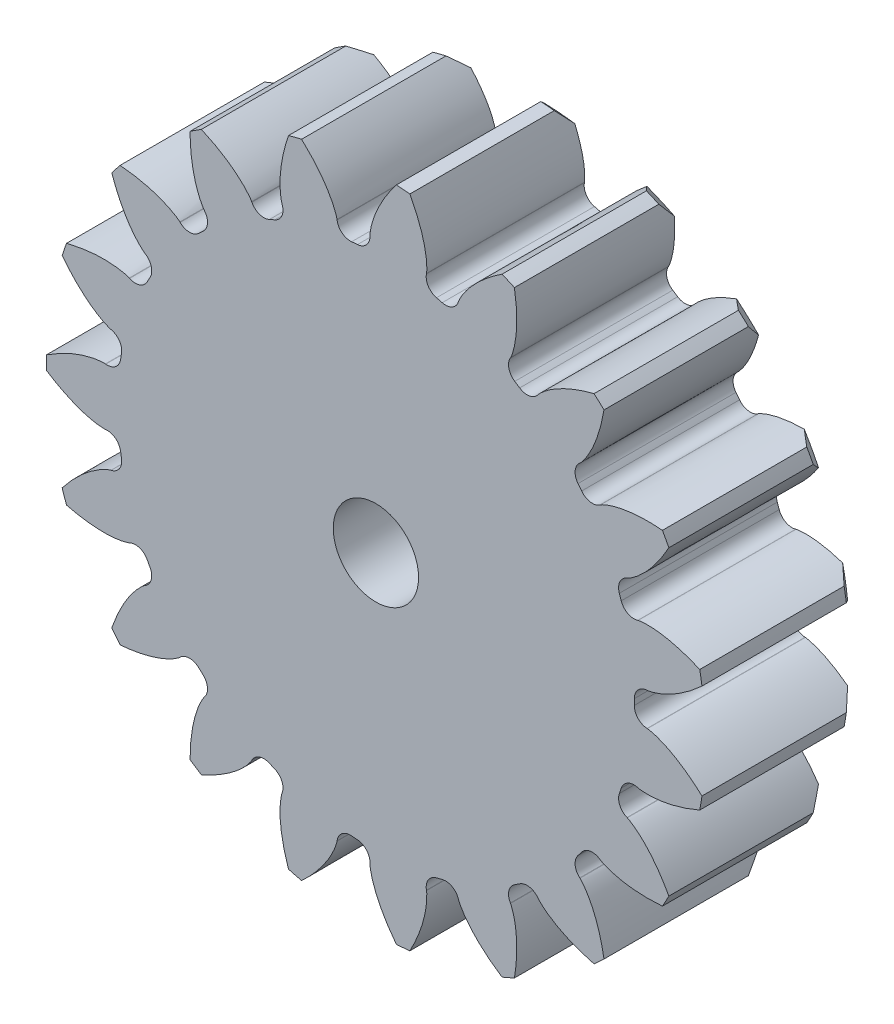
SolidWorks part; units mm, degrees
ref_plane "Front Plane" through (0, 0, 0) normal (0, 0, 1) x (1, 0, 0)
ref_plane "Top Plane" through (0, 0, 0) normal (0, 1, 0) x (1, 0, 0)
ref_plane "Right Plane" through (0, 0, 0) normal (1, 0, 0) x (0, 0, -1)
ref_axis "Axis1" through (0, 0, -0.2618) along (0, 0, 1)
sketch "Sketch1" plane through (0, 0, 0) normal (0, 0, 1) x (1, 0, 0)
  circle A0 centre (0, 0) radius 10.5
  dimension "D1" = 21
extrude "Boss-Extrude1" add sketch "Sketch1" along normal blind 5
sketch "Sketch2" plane through (0, 0, 5) normal (0, 0, 1) x (1, 0, 0)
  line L0 (0, 0) -> (8.2385, 0.4346) construction
  line L1 (8.2385, 0.4346) -> (8.598, 0.4535)
  line L2 (0, 0) -> (8.2385, -0.4346) construction
  line L3 (8.2385, -0.4346) -> (8.598, -0.4535)
  circle A0 centre (0, 0) radius 9.5 construction
  circle A1 centre (0, 0) radius 10.5 construction
  circle A2 centre (0, 0) radius 8.6099 construction
  circle A3 centre (0, 0) radius 8.25 construction
  arc A4 (8.2385, 0.4346) -> (8.2385, -0.4346) centre (0, 0) cw
  arc A5 (10.3953, 1.479) -> (10.3953, -1.479) centre (0, 0) cw
  spline S0 degree 4 poles (8.598, 0.4535) (8.6011, 0.4537) (8.6097, 0.4545) (8.6261, 0.4564) (8.6527, 0.4603) (8.7019, 0.4694) (8.7606, 0.483) (8.8264, 0.5011) (8.8966, 0.5233) (8.9562, 0.544) (9.0154, 0.5662) (9.074, 0.5897) (9.1445, 0.6198) (9.2284, 0.6582) (9.3256, 0.7063) (9.4345, 0.7648) (9.5442, 0.8285) (9.6509, 0.8946) (9.7572, 0.9651) (9.8591, 1.0361) (9.9633, 1.1136) (10.0586, 1.1871) (10.1636, 1.2736) (10.2478, 1.3447) (10.3567, 1.4428) (10.4204, 1.502) (10.4941, 1.5728) (10.5265, 1.605) (10.5464, 1.6249) knots 0 0 0 0 0 0.005377 0.015084 0.028532 0.04661 0.092111 0.119476 0.146842 0.174209 0.201575 0.228941 0.256307 0.307035 0.361767 0.4165 0.471232 0.525964 0.580697 0.635429 0.690161 0.744894 0.799626 0.854358 0.909091 0.954545 1 1 1 1 1 construction
  spline S1 degree 4 poles (8.598, 0.4535) (8.6011, 0.4537) (8.6097, 0.4545) (8.6261, 0.4564) (8.6527, 0.4603) (8.7019, 0.4694) (8.7606, 0.483) (8.8264, 0.5011) (8.8966, 0.5233) (8.9562, 0.544) (9.0154, 0.5662) (9.074, 0.5897) (9.1445, 0.6198) (9.2284, 0.6582) (9.3256, 0.7063) (9.4345, 0.7648) (9.5442, 0.8285) (9.6509, 0.8946) (9.7572, 0.9651) (9.8591, 1.0361) (9.9633, 1.1136) (10.0586, 1.1871) (10.1636, 1.2736) (10.2478, 1.3447) (10.3331, 1.4215) (10.3743, 1.4594) (10.3953, 1.479) knots 0 0 0 0 0 0.005377 0.015084 0.028532 0.04661 0.092111 0.119476 0.146842 0.174209 0.201575 0.228941 0.256307 0.307035 0.361767 0.4165 0.471232 0.525964 0.580697 0.635429 0.690161 0.744894 0.799626 0.854358 0.909091 0.909091 0.909091 0.909091 0.909091
  spline S2 degree 4 poles (8.598, -0.4535) (8.6011, -0.4537) (8.6097, -0.4545) (8.6261, -0.4564) (8.6527, -0.4603) (8.7019, -0.4694) (8.7606, -0.483) (8.8264, -0.5011) (8.8966, -0.5233) (8.9562, -0.544) (9.0154, -0.5662) (9.074, -0.5897) (9.1445, -0.6198) (9.2284, -0.6582) (9.3256, -0.7063) (9.4345, -0.7648) (9.5442, -0.8285) (9.6509, -0.8946) (9.7572, -0.9651) (9.8591, -1.0361) (9.9633, -1.1136) (10.0586, -1.1871) (10.1636, -1.2736) (10.2478, -1.3447) (10.3567, -1.4428) (10.4204, -1.502) (10.4941, -1.5728) (10.5265, -1.605) (10.5464, -1.6249) knots 0 0 0 0 0 0.005377 0.015084 0.028532 0.04661 0.092111 0.119476 0.146842 0.174209 0.201575 0.228941 0.256307 0.307035 0.361767 0.4165 0.471232 0.525964 0.580697 0.635429 0.690161 0.744894 0.799626 0.854358 0.909091 0.954545 1 1 1 1 1 construction
  spline S3 degree 4 poles (8.598, -0.4535) (8.6011, -0.4537) (8.6097, -0.4545) (8.6261, -0.4564) (8.6527, -0.4603) (8.7019, -0.4694) (8.7606, -0.483) (8.8264, -0.5011) (8.8966, -0.5233) (8.9562, -0.544) (9.0154, -0.5662) (9.074, -0.5897) (9.1445, -0.6198) (9.2284, -0.6582) (9.3256, -0.7063) (9.4345, -0.7648) (9.5442, -0.8285) (9.6509, -0.8946) (9.7572, -0.9651) (9.8591, -1.0361) (9.9633, -1.1136) (10.0586, -1.1871) (10.1636, -1.2736) (10.2478, -1.3447) (10.3331, -1.4215) (10.3743, -1.4594) (10.3953, -1.479) knots 0 0 0 0 0 0.005377 0.015084 0.028532 0.04661 0.092111 0.119476 0.146842 0.174209 0.201575 0.228941 0.256307 0.307035 0.361767 0.4165 0.471232 0.525964 0.580697 0.635429 0.690161 0.744894 0.799626 0.854358 0.909091 0.909091 0.909091 0.909091 0.909091
  dimension "D1" = 21
  dimension "D2" = 19
  dimension "D3" = 17.2198
  dimension "D4" = 16.5
extrude "Cut-Extrude1" cut sketch "Sketch2" against normal through all
fillet "Fillet1" radius 0.3557 1 edges at (8.2385, 0.4346, 2.5)
fillet "Fillet2" radius 0.3557 1 edges at (8.2385, -0.4346, 2.5)
pattern_circular "CirPattern1" count 19 over 360 about axis through (0, 0, 5) along (0, 0, -1) of "Cut-Extrude1", "Fillet1", "Fillet2"
sketch "Sketch4" plane through (0, 0, 5) normal (0, 0, 1) x (1, 0, 0)
  circle A0 centre (0, 0) radius 1.35
  dimension "D1" = 2.7
extrude "Bore" cut sketch "Sketch4" against normal through all
sketch "Sketch5" plane through (0, 0, 5) normal (0, 0, 1) x (1, 0, 0)
  line L44 (8.298, 2.2953) -> (8.2874, 2.2923)
  line L45 (8.298, 2.2953) -> (8.2874, 2.2923)
  line L46 (7.9479, 3.2813) -> (7.9582, 3.2854)
  line L47 (7.9479, 3.2813) -> (7.9582, 3.2854)
  line L108 (-2.9728, 8.0801) -> (-2.9688, 8.0698)
  line L109 (-3.9264, 7.6498) -> (-3.9314, 7.6597)
  line L110 (-5.4353, 6.6771) -> (-5.4282, 6.6686)
  line L111 (-6.1975, 5.9604) -> (-6.2054, 5.9681)
  line L112 (-7.3089, 4.5505) -> (-7.2994, 4.5447)
  line L113 (-7.7971, 3.6251) -> (-7.8071, 3.6299)
  line L114 (-8.3904, 1.9307) -> (-8.3796, 1.9283)
  line L115 (-8.5517, 0.897) -> (-8.5627, 0.8982)
  line L116 (-8.5627, -0.8982) -> (-8.5517, -0.897)
  line L117 (-8.3796, -1.9283) -> (-8.3904, -1.9307)
  line L118 (-7.8071, -3.6299) -> (-7.7971, -3.6251)
  line L119 (-7.2994, -4.5447) -> (-7.3089, -4.5505)
  line L120 (-6.2054, -5.9681) -> (-6.1975, -5.9604)
  line L121 (-5.4282, -6.6686) -> (-5.4353, -6.6771)
  line L122 (-3.9314, -7.6597) -> (-3.9264, -7.6498)
  line L123 (-2.9688, -8.0698) -> (-2.9728, -8.0801)
  line L124 (-1.2313, -8.5212) -> (-1.2298, -8.5102)
  line L125 (-0.1877, -8.5965) -> (-0.1881, -8.6076)
  line L126 (1.6023, -8.4592) -> (1.6001, -8.4484)
  line L127 (2.6137, -8.1917) -> (2.617, -8.2023)
  line L128 (4.2622, -7.4806) -> (4.2566, -7.4711)
  line L129 (5.132, -6.8992) -> (5.1385, -6.9081)
  line L130 (6.4602, -5.6914) -> (6.4518, -5.6842)
  line L131 (7.0941, -4.859) -> (7.1031, -4.8653)
  line L132 (7.9582, -3.2854) -> (7.9479, -3.2813)
  line L133 (8.2874, -2.2923) -> (8.298, -2.2953)
  line L134 (8.5937, -0.5234) -> (8.5827, -0.5228)
  line L135 (8.5827, 0.5228) -> (8.5937, 0.5234)
  line L136 (7.1031, 4.8653) -> (7.0941, 4.859)
  line L137 (6.4518, 5.6842) -> (6.4602, 5.6914)
  line L138 (5.1385, 6.9081) -> (5.132, 6.8992)
  line L139 (4.2566, 7.4711) -> (4.2622, 7.4806)
  line L140 (2.617, 8.2023) -> (2.6137, 8.1917)
  line L141 (1.6001, 8.4484) -> (1.6023, 8.4592)
  line L142 (-0.1881, 8.6076) -> (-0.1877, 8.5965)
  line L143 (-1.2298, 8.5102) -> (-1.2313, 8.5212)
  line L144 (-2.9728, 8.0801) -> (-2.9688, 8.0698)
  line L145 (-3.9264, 7.6498) -> (-3.9314, 7.6597)
  line L146 (-5.4353, 6.6771) -> (-5.4282, 6.6686)
  line L147 (-6.1975, 5.9604) -> (-6.2054, 5.9681)
  line L148 (-7.3089, 4.5505) -> (-7.2994, 4.5447)
  line L149 (-7.7971, 3.6251) -> (-7.8071, 3.6299)
  line L150 (-8.3904, 1.9307) -> (-8.3796, 1.9283)
  line L151 (-8.5517, 0.897) -> (-8.5627, 0.8982)
  line L152 (-8.5627, -0.8982) -> (-8.5517, -0.897)
  line L153 (-8.3796, -1.9283) -> (-8.3904, -1.9307)
  line L154 (-7.8071, -3.6299) -> (-7.7971, -3.6251)
  line L155 (-7.2994, -4.5447) -> (-7.3089, -4.5505)
  line L156 (-6.2054, -5.9681) -> (-6.1975, -5.9604)
  line L157 (-5.4282, -6.6686) -> (-5.4353, -6.6771)
  line L158 (-3.9314, -7.6597) -> (-3.9264, -7.6498)
  line L159 (-2.9688, -8.0698) -> (-2.9728, -8.0801)
  line L160 (-1.2313, -8.5212) -> (-1.2298, -8.5102)
  line L161 (-0.1877, -8.5965) -> (-0.1881, -8.6076)
  line L162 (1.6023, -8.4592) -> (1.6001, -8.4484)
  line L163 (2.6137, -8.1917) -> (2.617, -8.2023)
  line L164 (4.2622, -7.4806) -> (4.2566, -7.4711)
  line L165 (5.132, -6.8992) -> (5.1385, -6.9081)
  line L166 (6.4602, -5.6914) -> (6.4518, -5.6842)
  line L167 (7.0941, -4.859) -> (7.1031, -4.8653)
  line L168 (7.9582, -3.2854) -> (7.9479, -3.2813)
  line L169 (8.2874, -2.2923) -> (8.298, -2.2953)
  line L170 (8.5937, -0.5234) -> (8.5827, -0.5228)
  line L171 (8.5827, 0.5228) -> (8.5937, 0.5234)
  line L172 (7.1031, 4.8653) -> (7.0941, 4.859)
  line L173 (6.4518, 5.6842) -> (6.4602, 5.6914)
  line L174 (5.1385, 6.9081) -> (5.132, 6.8992)
  line L175 (4.2566, 7.4711) -> (4.2622, 7.4806)
  line L176 (2.617, 8.2023) -> (2.6137, 8.1917)
  line L177 (1.6001, 8.4484) -> (1.6023, 8.4592)
  line L178 (-0.1881, 8.6076) -> (-0.1877, 8.5965)
  line L179 (-1.2298, 8.5102) -> (-1.2313, 8.5212)
  arc A88 (7.7665, 2.568) -> (8.2874, 2.2923) centre (8.1706, 2.7016) ccw
  arc A89 (7.7665, 2.568) -> (8.2874, 2.2923) centre (8.1706, 2.7016) ccw
  arc A90 (7.7665, 2.568) -> (7.7061, 2.7437) centre (0, 0) ccw
  arc A91 (7.7665, 2.568) -> (7.7061, 2.7437) centre (0, 0) ccw
  arc A92 (7.9479, 3.2813) -> (7.7061, 2.7437) centre (8.1071, 2.8865) ccw
  arc A93 (7.9479, 3.2813) -> (7.7061, 2.7437) centre (8.1071, 2.8865) ccw
  arc A94 (9.2728, 4.7749) -> (9.0692, 5.1512) centre (0, 0) ccw
  arc A95 (9.2728, 4.7749) -> (9.0692, 5.1512) centre (0, 0) ccw
  circle A144 centre (0, 0) radius 21
  arc A216 (-2.3525, 10.1612) -> (-2.7673, 10.0562) centre (0, 0) ccw
  arc A217 (-3.2006, 7.5279) -> (-2.9688, 8.0698) centre (-3.3671, 7.9196) ccw
  arc A218 (-3.2006, 7.5279) -> (-3.3707, 7.4532) centre (0, 0) ccw
  arc A219 (-3.9264, 7.6498) -> (-3.3707, 7.4532) centre (-3.5461, 7.8411) ccw
  arc A220 (-5.5244, 8.8468) -> (-5.8826, 8.6128) centre (0, 0) ccw
  arc A221 (-5.4715, 6.0808) -> (-5.4282, 6.6686) centre (-5.7562, 6.3972) ccw
  arc A222 (-5.4715, 6.0808) -> (-5.6082, 5.9549) centre (0, 0) ccw
  arc A223 (-6.1975, 5.9604) -> (-5.6082, 5.9549) centre (-5.9, 6.2648) ccw
  arc A224 (-8.0976, 6.5737) -> (-8.3604, 6.2361) centre (0, 0) ccw
  arc A225 (-7.1494, 3.9747) -> (-7.2994, 4.5447) centre (-7.5214, 4.1815) ccw
  arc A226 (-7.1494, 3.9747) -> (-7.2379, 3.8113) centre (0, 0) ccw
  arc A227 (-7.7971, 3.6251) -> (-7.2379, 3.8113) centre (-7.6145, 4.0096) ccw
  arc A228 (-9.7933, 3.5882) -> (-9.9323, 3.1836) centre (0, 0) ccw
  arc A229 (-8.0526, 1.4379) -> (-8.3796, 1.9283) centre (-8.4716, 1.5128) ccw
  arc A230 (-8.0526, 1.4379) -> (-8.0832, 1.2547) centre (0, 0) ccw
  arc A231 (-8.5517, 0.897) -> (-8.0832, 1.2547) centre (-8.5038, 1.3199) ccw
  arc A232 (-10.4278, 0.2139) -> (-10.4278, -0.2139) centre (0, 0) ccw
  arc A233 (-8.0832, -1.2547) -> (-8.5517, -0.897) centre (-8.5038, -1.3199) ccw
  arc A234 (-8.0832, -1.2547) -> (-8.0526, -1.4379) centre (0, 0) ccw
  arc A235 (-8.3796, -1.9283) -> (-8.0526, -1.4379) centre (-8.4716, -1.5128) ccw
  arc A236 (-9.9323, -3.1836) -> (-9.7933, -3.5882) centre (0, 0) ccw
  arc A237 (-7.2379, -3.8113) -> (-7.7971, -3.6251) centre (-7.6145, -4.0096) ccw
  arc A238 (-7.2379, -3.8113) -> (-7.1494, -3.9747) centre (0, 0) ccw
  arc A239 (-7.2994, -4.5447) -> (-7.1494, -3.9747) centre (-7.5214, -4.1815) ccw
  arc A240 (-8.3604, -6.2361) -> (-8.0976, -6.5737) centre (0, 0) ccw
  arc A241 (-5.6082, -5.9549) -> (-6.1975, -5.9604) centre (-5.9, -6.2648) ccw
  arc A242 (-5.6082, -5.9549) -> (-5.4715, -6.0808) centre (0, 0) ccw
  arc A243 (-5.4282, -6.6686) -> (-5.4715, -6.0808) centre (-5.7562, -6.3972) ccw
  arc A244 (-5.8826, -8.6128) -> (-5.5244, -8.8468) centre (0, 0) ccw
  arc A245 (-3.3707, -7.4532) -> (-3.9264, -7.6498) centre (-3.5461, -7.8411) ccw
  arc A246 (-3.3707, -7.4532) -> (-3.2006, -7.5279) centre (0, 0) ccw
  arc A247 (-2.9688, -8.0698) -> (-3.2006, -7.5279) centre (-3.3671, -7.9196) ccw
  arc A248 (-2.7673, -10.0562) -> (-2.3525, -10.1612) centre (0, 0) ccw
  arc A249 (-0.768, -8.1439) -> (-1.2298, -8.5102) centre (-0.808, -8.5676) ccw
  arc A250 (-0.768, -8.1439) -> (-0.5829, -8.1592) centre (0, 0) ccw
  arc A251 (-0.1877, -8.5965) -> (-0.5829, -8.1592) centre (-0.6132, -8.5838) ccw
  arc A252 (0.6479, -10.4099) -> (1.0743, -10.3745) centre (0, 0) ccw
  arc A253 (1.9179, -7.952) -> (1.6001, -8.4484) centre (2.0177, -8.3658) ccw
  arc A254 (1.9179, -7.952) -> (2.098, -7.9064) centre (0, 0) ccw
  arc A255 (2.6137, -8.1917) -> (2.098, -7.9064) centre (2.2072, -8.3178) ccw
  arc A256 (3.9929, -9.6354) -> (4.3847, -9.4636) centre (0, 0) ccw
  arc A257 (4.396, -6.8984) -> (4.2566, -7.4711) centre (4.6247, -7.2574) ccw
  arc A258 (4.396, -6.8984) -> (4.5515, -6.7968) centre (0, 0) ccw
  arc A259 (5.132, -6.8992) -> (4.5515, -6.7968) centre (4.7884, -7.1504) ccw
  arc A260 (6.9052, -7.8169) -> (7.22, -7.5271) centre (0, 0) ccw
  arc A261 (6.3977, -5.0973) -> (6.4518, -5.6842) centre (6.7306, -5.3625) ccw
  arc A262 (6.3977, -5.0973) -> (6.5118, -4.9506) centre (0, 0) ccw
  arc A263 (7.0941, -4.859) -> (6.5118, -4.9506) centre (6.8507, -5.2082) ccw
  arc A264 (9.0692, -5.1512) -> (9.2728, -4.7749) centre (0, 0) ccw
  arc A265 (7.7061, -2.7437) -> (7.9479, -3.2813) centre (8.1071, -2.8865) ccw
  arc A266 (7.7061, -2.7437) -> (7.7665, -2.568) centre (0, 0) ccw
  arc A267 (8.2874, -2.2923) -> (7.7665, -2.568) centre (8.1706, -2.7016) ccw
  arc A268 (10.2504, -1.9274) -> (10.3208, -1.5054) centre (0, 0) ccw
  arc A269 (8.1795, -0.0929) -> (8.5827, -0.5228) centre (8.6051, -0.0977) ccw
  arc A270 (8.1795, -0.0929) -> (8.1795, 0.0929) centre (0, 0) ccw
  arc A271 (8.5827, 0.5228) -> (8.1795, 0.0929) centre (8.6051, 0.0977) ccw
  arc A272 (10.3208, 1.5054) -> (10.2504, 1.9274) centre (0, 0) ccw
  arc A273 (6.5118, 4.9506) -> (7.0941, 4.859) centre (6.8507, 5.2082) ccw
  arc A274 (6.5118, 4.9506) -> (6.3977, 5.0973) centre (0, 0) ccw
  arc A275 (6.4518, 5.6842) -> (6.3977, 5.0973) centre (6.7306, 5.3625) ccw
  arc A276 (7.22, 7.5271) -> (6.9052, 7.8169) centre (0, 0) ccw
  arc A277 (4.5515, 6.7968) -> (5.132, 6.8992) centre (4.7884, 7.1504) ccw
  arc A278 (4.5515, 6.7968) -> (4.396, 6.8984) centre (0, 0) ccw
  arc A279 (4.2566, 7.4711) -> (4.396, 6.8984) centre (4.6247, 7.2574) ccw
  arc A280 (4.3847, 9.4636) -> (3.9929, 9.6354) centre (0, 0) ccw
  arc A281 (2.098, 7.9064) -> (2.6137, 8.1917) centre (2.2072, 8.3178) ccw
  arc A282 (2.098, 7.9064) -> (1.9179, 7.952) centre (0, 0) ccw
  arc A283 (1.6001, 8.4484) -> (1.9179, 7.952) centre (2.0177, 8.3658) ccw
  arc A284 (1.0743, 10.3745) -> (0.6479, 10.4099) centre (0, 0) ccw
  arc A285 (-0.5829, 8.1592) -> (-0.1877, 8.5965) centre (-0.6132, 8.5838) ccw
  arc A286 (-0.5829, 8.1592) -> (-0.768, 8.1439) centre (0, 0) ccw
  arc A287 (-1.2298, 8.5102) -> (-0.768, 8.1439) centre (-0.808, 8.5676) ccw
  arc A288 (-2.3525, 10.1612) -> (-2.7673, 10.0562) centre (0, 0) ccw
  arc A289 (-3.2006, 7.5279) -> (-2.9688, 8.0698) centre (-3.3671, 7.9196) ccw
  arc A290 (-3.2006, 7.5279) -> (-3.3707, 7.4532) centre (0, 0) ccw
  arc A291 (-3.9264, 7.6498) -> (-3.3707, 7.4532) centre (-3.5461, 7.8411) ccw
  arc A292 (-5.5244, 8.8468) -> (-5.8826, 8.6128) centre (0, 0) ccw
  arc A293 (-5.4715, 6.0808) -> (-5.4282, 6.6686) centre (-5.7562, 6.3972) ccw
  arc A294 (-5.4715, 6.0808) -> (-5.6082, 5.9549) centre (0, 0) ccw
  arc A295 (-6.1975, 5.9604) -> (-5.6082, 5.9549) centre (-5.9, 6.2648) ccw
  arc A296 (-8.0976, 6.5737) -> (-8.3604, 6.2361) centre (0, 0) ccw
  arc A297 (-7.1494, 3.9747) -> (-7.2994, 4.5447) centre (-7.5214, 4.1815) ccw
  arc A298 (-7.1494, 3.9747) -> (-7.2379, 3.8113) centre (0, 0) ccw
  arc A299 (-7.7971, 3.6251) -> (-7.2379, 3.8113) centre (-7.6145, 4.0096) ccw
  arc A300 (-9.7933, 3.5882) -> (-9.9323, 3.1836) centre (0, 0) ccw
  arc A301 (-8.0526, 1.4379) -> (-8.3796, 1.9283) centre (-8.4716, 1.5128) ccw
  arc A302 (-8.0526, 1.4379) -> (-8.0832, 1.2547) centre (0, 0) ccw
  arc A303 (-8.5517, 0.897) -> (-8.0832, 1.2547) centre (-8.5038, 1.3199) ccw
  arc A304 (-10.4278, 0.2139) -> (-10.4278, -0.2139) centre (0, 0) ccw
  arc A305 (-8.0832, -1.2547) -> (-8.5517, -0.897) centre (-8.5038, -1.3199) ccw
  arc A306 (-8.0832, -1.2547) -> (-8.0526, -1.4379) centre (0, 0) ccw
  arc A307 (-8.3796, -1.9283) -> (-8.0526, -1.4379) centre (-8.4716, -1.5128) ccw
  arc A308 (-9.9323, -3.1836) -> (-9.7933, -3.5882) centre (0, 0) ccw
  arc A309 (-7.2379, -3.8113) -> (-7.7971, -3.6251) centre (-7.6145, -4.0096) ccw
  arc A310 (-7.2379, -3.8113) -> (-7.1494, -3.9747) centre (0, 0) ccw
  arc A311 (-7.2994, -4.5447) -> (-7.1494, -3.9747) centre (-7.5214, -4.1815) ccw
  arc A312 (-8.3604, -6.2361) -> (-8.0976, -6.5737) centre (0, 0) ccw
  arc A313 (-5.6082, -5.9549) -> (-6.1975, -5.9604) centre (-5.9, -6.2648) ccw
  arc A314 (-5.6082, -5.9549) -> (-5.4715, -6.0808) centre (0, 0) ccw
  arc A315 (-5.4282, -6.6686) -> (-5.4715, -6.0808) centre (-5.7562, -6.3972) ccw
  arc A316 (-5.8826, -8.6128) -> (-5.5244, -8.8468) centre (0, 0) ccw
  arc A317 (-3.3707, -7.4532) -> (-3.9264, -7.6498) centre (-3.5461, -7.8411) ccw
  arc A318 (-3.3707, -7.4532) -> (-3.2006, -7.5279) centre (0, 0) ccw
  arc A319 (-2.9688, -8.0698) -> (-3.2006, -7.5279) centre (-3.3671, -7.9196) ccw
  arc A320 (-2.7673, -10.0562) -> (-2.3525, -10.1612) centre (0, 0) ccw
  arc A321 (-0.768, -8.1439) -> (-1.2298, -8.5102) centre (-0.808, -8.5676) ccw
  arc A322 (-0.768, -8.1439) -> (-0.5829, -8.1592) centre (0, 0) ccw
  arc A323 (-0.1877, -8.5965) -> (-0.5829, -8.1592) centre (-0.6132, -8.5838) ccw
  arc A324 (0.6479, -10.4099) -> (1.0743, -10.3745) centre (0, 0) ccw
  arc A325 (1.9179, -7.952) -> (1.6001, -8.4484) centre (2.0177, -8.3658) ccw
  arc A326 (1.9179, -7.952) -> (2.098, -7.9064) centre (0, 0) ccw
  arc A327 (2.6137, -8.1917) -> (2.098, -7.9064) centre (2.2072, -8.3178) ccw
  arc A328 (3.9929, -9.6354) -> (4.3847, -9.4636) centre (0, 0) ccw
  arc A329 (4.396, -6.8984) -> (4.2566, -7.4711) centre (4.6247, -7.2574) ccw
  arc A330 (4.396, -6.8984) -> (4.5515, -6.7968) centre (0, 0) ccw
  arc A331 (5.132, -6.8992) -> (4.5515, -6.7968) centre (4.7884, -7.1504) ccw
  arc A332 (6.9052, -7.8169) -> (7.22, -7.5271) centre (0, 0) ccw
  arc A333 (6.3977, -5.0973) -> (6.4518, -5.6842) centre (6.7306, -5.3625) ccw
  arc A334 (6.3977, -5.0973) -> (6.5118, -4.9506) centre (0, 0) ccw
  arc A335 (7.0941, -4.859) -> (6.5118, -4.9506) centre (6.8507, -5.2082) ccw
  arc A336 (9.0692, -5.1512) -> (9.2728, -4.7749) centre (0, 0) ccw
  arc A337 (7.7061, -2.7437) -> (7.9479, -3.2813) centre (8.1071, -2.8865) ccw
  arc A338 (7.7061, -2.7437) -> (7.7665, -2.568) centre (0, 0) ccw
  arc A339 (8.2874, -2.2923) -> (7.7665, -2.568) centre (8.1706, -2.7016) ccw
  arc A340 (10.2504, -1.9274) -> (10.3208, -1.5054) centre (0, 0) ccw
  arc A341 (8.1795, -0.0929) -> (8.5827, -0.5228) centre (8.6051, -0.0977) ccw
  arc A342 (8.1795, -0.0929) -> (8.1795, 0.0929) centre (0, 0) ccw
  arc A343 (8.5827, 0.5228) -> (8.1795, 0.0929) centre (8.6051, 0.0977) ccw
  arc A344 (10.3208, 1.5054) -> (10.2504, 1.9274) centre (0, 0) ccw
  arc A345 (6.5118, 4.9506) -> (7.0941, 4.859) centre (6.8507, 5.2082) ccw
  arc A346 (6.5118, 4.9506) -> (6.3977, 5.0973) centre (0, 0) ccw
  arc A347 (6.4518, 5.6842) -> (6.3977, 5.0973) centre (6.7306, 5.3625) ccw
  arc A348 (7.22, 7.5271) -> (6.9052, 7.8169) centre (0, 0) ccw
  arc A349 (4.5515, 6.7968) -> (5.132, 6.8992) centre (4.7884, 7.1504) ccw
  arc A350 (4.5515, 6.7968) -> (4.396, 6.8984) centre (0, 0) ccw
  arc A351 (4.2566, 7.4711) -> (4.396, 6.8984) centre (4.6247, 7.2574) ccw
  arc A352 (4.3847, 9.4636) -> (3.9929, 9.6354) centre (0, 0) ccw
  arc A353 (2.098, 7.9064) -> (2.6137, 8.1917) centre (2.2072, 8.3178) ccw
  arc A354 (2.098, 7.9064) -> (1.9179, 7.952) centre (0, 0) ccw
  arc A355 (1.6001, 8.4484) -> (1.9179, 7.952) centre (2.0177, 8.3658) ccw
  arc A356 (1.0743, 10.3745) -> (0.6479, 10.4099) centre (0, 0) ccw
  arc A357 (-0.5829, 8.1592) -> (-0.1877, 8.5965) centre (-0.6132, 8.5838) ccw
  arc A358 (-0.5829, 8.1592) -> (-0.768, 8.1439) centre (0, 0) ccw
  arc A359 (-1.2298, 8.5102) -> (-0.768, 8.1439) centre (-0.808, 8.5676) ccw
  spline S44 degree 3 poles (-282.4949, 1980.3381) (17.3696, -124.1446) (27.3941, -1.6737) (9.1321, 2.2785) (8.9654, 2.3045) (8.7149, 2.3225) (8.5896, 2.3263) (8.4646, 2.3191) (5.5919, 2.0348) (2.7812, 0.3541) (28.9551, -1997.2705) knots -27.101219 -27.101219 -27.101219 -27.101219 0.5 0.5 0.75 0.75 0.875 0.9375 0.9375 5.184556 5.184556 5.184556 5.184556 only from (10.2504, 1.9274) to (8.298, 2.2953)
  spline S45 degree 3 poles (10.2504, 1.9274) (9.9425, 2.0622) (9.6239, 2.172) (9.1321, 2.2785) (8.9654, 2.3045) (8.7149, 2.3225) (8.5896, 2.3263) (8.4646, 2.3191) (8.3813, 2.3109) (8.3396, 2.3064) (8.298, 2.2953) knots 0 0 0 0 0.5 0.5 0.75 0.75 0.875 0.9375 0.9375 1 1 1 1
  spline S46 degree 3 poles (-1106.7683, 1663.5843) (2.3045, 1.6388) (5.6377, 1.8142) (8.1038, 3.3687) (8.1382, 3.3925) (8.2395, 3.4668) (8.3045, 3.5206) (8.4912, 3.6889) (8.606, 3.8111) (20.622, 18.1865) (-64.0336, 107.6431) (1073.2628, -1688.666) knots -4.22776 -4.22776 -4.22776 -4.22776 0.0625 0.0625 0.125 0.125 0.25 0.25 0.5 0.5 28.150012 28.150012 28.150012 28.150012 only from (7.9582, 3.2854) to (9.2728, 4.7749)
  spline S47 degree 3 poles (7.9582, 3.2854) (7.9974, 3.302) (8.033, 3.3241) (8.1038, 3.3687) (8.1382, 3.3925) (8.2395, 3.4668) (8.3045, 3.5206) (8.4912, 3.6889) (8.606, 3.8111) (8.9291, 4.1975) (9.1128, 4.4797) (9.2728, 4.7749) knots 0 0 0 0 0.0625 0.0625 0.125 0.125 0.25 0.25 0.5 0.5 1 1 1 1
  spline S108 degree 3 poles (-1884.3746, -664.5157) (-1.023, 2.6362) (-0.3748, 5.9106) (-1.2763, 8.6828) (-1.2908, 8.722) (-1.338, 8.8385) (-1.3742, 8.9146) (-1.4915, 9.1369) (-1.5818, 9.2783) (-12.5676, 24.4555) (-120.0686, -35.6494) (1900.4637, 625.8783) knots -4.22776 -4.22776 -4.22776 -4.22776 0.0625 0.0625 0.125 0.125 0.25 0.25 0.5 0.5 28.150012 28.150012 28.150012 28.150012 only from (-1.2313, 8.5212) to (-2.3525, 10.1612)
  spline S109 degree 3 poles (-1950.246, -445.0651) (122.2862, 27.562) (-0.5942, 27.4387) (-3.0248, 8.9128) (-3.037, 8.7445) (-3.0342, 8.4933) (-3.0276, 8.3682) (-3.0102, 8.2442) (-2.4896, 5.4048) (-0.5825, 2.7425) (1988.0577, 193.7895) knots -27.101219 -27.101219 -27.101219 -27.101219 0.5 0.5 0.75 0.75 0.875 0.9375 0.9375 5.184556 5.184556 5.184556 5.184556 only from (-2.7673, 10.0562) to (-2.9728, 8.0801)
  spline S110 degree 3 poles (-1566.5061, -1240.3658) (-1.8235, 2.1612) (-2.2736, 5.4686) (-4.0264, 7.7979) (-4.0529, 7.8303) (-4.1354, 7.9251) (-4.1943, 7.9854) (-4.3775, 8.1576) (-4.5087, 8.2619) (-19.8274, 19.0497) (-101.9876, -72.704) (1594.269, 1209.046) knots -4.22776 -4.22776 -4.22776 -4.22776 0.0625 0.0625 0.125 0.125 0.25 0.25 0.5 0.5 28.150012 28.150012 28.150012 28.150012 only from (-3.9314, 7.6597) to (-5.5244, 8.8468)
  spline S111 degree 3 poles (-1700.0639, -1054.194) (106.7111, 65.7749) (-9.4714, 25.7591) (-5.7549, 7.4477) (-5.7118, 7.2846) (-5.6276, 7.0479) (-5.5808, 6.9317) (-5.524, 6.8201) (-4.1097, 4.3036) (-1.4414, 2.4048) (1817.4159, 828.8107) knots -27.101219 -27.101219 -27.101219 -27.101219 0.5 0.5 0.75 0.75 0.875 0.9375 0.9375 5.184556 5.184556 5.184556 5.184556 only from (-5.8826, 8.6128) to (-5.4353, 6.6771)
  spline S112 degree 3 poles (-1078.8823, -1681.8031) (-2.4265, 1.4521) (-3.9261, 4.4341) (-6.3402, 6.068) (-6.3758, 6.09) (-6.4846, 6.1529) (-6.5599, 6.1908) (-6.7891, 6.2942) (-6.9471, 6.3503) (-24.9385, 11.5796) (-72.8546, -101.88) (1115.3105, 1661.1949) knots -4.22776 -4.22776 -4.22776 -4.22776 0.0625 0.0625 0.125 0.125 0.25 0.25 0.5 0.5 28.150012 28.150012 28.150012 28.150012 only from (-6.2054, 5.9681) to (-8.0976, 6.5737)
  spline S113 degree 3 poles (-1265.6535, -1549.0847) (79.5721, 96.8601) (-17.3221, 21.2881) (-7.8614, 5.1756) (-7.7676, 5.0353) (-7.6111, 4.8387) (-7.5291, 4.7441) (-7.4391, 4.6569) (-5.2843, 2.736) (-2.1442, 1.8064) (1449.8289, 1374.0174) knots -27.101219 -27.101219 -27.101219 -27.101219 0.5 0.5 0.75 0.75 0.875 0.9375 0.9375 5.184556 5.184556 5.184556 5.184556 only from (-8.3604, 6.2361) to (-7.3089, 4.5505)
  spline S114 degree 3 poles (-474.3449, -1940.9909) (-2.7665, 0.5855) (-5.1531, 2.919) (-7.967, 3.6806) (-8.0078, 3.6898) (-8.1311, 3.714) (-8.2146, 3.7254) (-8.4649, 3.7488) (-8.6326, 3.7505) (-27.3472, 2.8547) (-35.8268, -120.0157) (515.4908, 1933.3275) knots -4.22776 -4.22776 -4.22776 -4.22776 0.0625 0.0625 0.125 0.125 0.25 0.25 0.5 0.5 28.150012 28.150012 28.150012 28.150012 only from (-7.8071, 3.6299) to (-9.7933, 3.5882)
  spline S115 degree 3 poles (-694.0899, -1876.1081) (43.8102, 117.4489) (-23.2958, 14.5101) (-9.1159, 2.3426) (-8.9817, 2.2403) (-8.7699, 2.1052) (-8.6615, 2.0423) (-8.5481, 1.9891) (-5.8864, 0.8719) (-2.6145, 1.0123) (925.1305, 1770.3281) knots -27.101219 -27.101219 -27.101219 -27.101219 0.5 0.5 0.75 0.75 0.875 0.9375 0.9375 5.184556 5.184556 5.184556 5.184556 only from (-9.9323, 3.1836) to (-8.3904, 1.9307)
  spline S116 degree 3 poles (181.5951, -1989.8422) (-2.8067, -0.3445) (-5.8217, 1.0877) (-8.7304, 0.8943) (-8.772, 0.8898) (-8.8965, 0.8726) (-8.9792, 0.8562) (-9.2235, 0.7971) (-9.3827, 0.7443) (-26.7923, -6.1796) (5.0835, -125.1459) (-140.1903, 1995.954) knots -4.22776 -4.22776 -4.22776 -4.22776 0.0625 0.0625 0.125 0.125 0.25 0.25 0.5 0.5 28.150012 28.150012 28.150012 28.150012 only from (-8.5627, 0.8982) to (-10.4278, 0.2139)
  spline S117 degree 3 poles (-47.3109, -1999.826) (3.3009, 125.3104) (-26.745, 6.1598) (-9.3826, -0.7443) (-9.2225, -0.7974) (-8.9783, -0.8564) (-8.8554, -0.8807) (-8.7308, -0.8943) (-5.8506, -1.0866) (-2.8016, 0.1086) (300.1798, 1974.7962) knots -27.101219 -27.101219 -27.101219 -27.101219 0.5 0.5 0.75 0.75 0.875 0.9375 0.9375 5.184556 5.184556 5.184556 5.184556 only from (-10.4278, -0.2139) to (-8.5627, -0.8982)
  spline S118 degree 3 poles (817.8565, -1823.0632) (-2.5428, -1.2372) (-5.8594, -0.8616) (-8.5477, -1.9889) (-8.5856, -2.0067) (-8.6978, -2.0633) (-8.7707, -2.1057) (-8.9826, -2.241) (-9.116, -2.3426) (-23.3342, -14.5442) (45.4428, -116.7146) (-780.6796, 1842.288) knots -4.22776 -4.22776 -4.22776 -4.22776 0.0625 0.0625 0.125 0.125 0.25 0.25 0.5 0.5 28.150012 28.150012 28.150012 28.150012 only from (-8.3904, -1.9307) to (-9.9323, -3.1836)
  spline S119 degree 3 poles (604.595, -1906.8317) (-37.5662, 119.5925) (-27.296, -2.8581) (-8.6326, -3.7505) (-8.4639, -3.7487) (-8.2137, -3.7252) (-8.0896, -3.7083) (-7.9674, -3.6807) (-5.1807, -2.9274) (-2.685, -0.807) (-357.3001, 1965.2645) knots -27.101219 -27.101219 -27.101219 -27.101219 0.5 0.5 0.75 0.75 0.875 0.9375 0.9375 5.184556 5.184556 5.184556 5.184556 only from (-9.7933, -3.5882) to (-7.8071, -3.6299)
  spline S120 degree 3 poles (1365.4904, -1458.7271) (-2.0033, -1.9958) (-5.2622, -2.7174) (-7.4388, -4.6566) (-7.4689, -4.6857) (-7.5565, -4.7757) (-7.6117, -4.8394) (-7.7682, -5.0362) (-7.8614, -5.1756) (-17.3474, -21.3327) (80.8778, -95.6354) (-1336.5702, 1488.9815) knots -4.22776 -4.22776 -4.22776 -4.22776 0.0625 0.0625 0.125 0.125 0.25 0.25 0.5 0.5 28.150012 28.150012 28.150012 28.150012 only from (-7.3089, -4.5505) to (-8.3604, -6.2361)
  spline S121 degree 3 poles (1190.9836, -1607.2027) (-74.3624, 100.9149) (-24.889, -11.5662) (-6.9471, -6.3503) (-6.7881, -6.2938) (-6.5591, -6.1904) (-6.4472, -6.1341) (-6.3406, -6.0683) (-3.9495, -4.451) (-2.2775, -1.6351) (-976.0609, 1742.7659) knots -27.101219 -27.101219 -27.101219 -27.101219 0.5 0.5 0.75 0.75 0.875 0.9375 0.9375 5.184556 5.184556 5.184556 5.184556 only from (-8.0976, -6.5737) to (-6.2054, -5.9681)
  spline S122 degree 3 poles (1765.1523, -936.3152) (-1.2467, -2.5381) (-4.0947, -4.2788) (-5.5237, -6.8196) (-5.5427, -6.8569) (-5.5964, -6.9706) (-5.6279, -7.0488) (-5.7121, -7.2856) (-5.7549, -7.4478) (-9.4807, -25.8096) (107.5483, -64.1926) (-1747.6226, 974.3207) knots -4.22776 -4.22776 -4.22776 -4.22776 0.0625 0.0625 0.125 0.125 0.25 0.25 0.5 0.5 28.150012 28.150012 28.150012 28.150012 only from (-5.4353, -6.6771) to (-5.8826, -8.6128)
  spline S123 degree 3 poles (1648.3107, -1133.4082) (-103.1003, 71.3017) (-19.7849, -19.0209) (-4.5087, -8.2619) (-4.3767, -8.1569) (-4.1937, -7.9847) (-4.1061, -7.8951) (-4.0267, -7.7983) (-2.2903, -5.4922) (-1.6232, -2.286) (-1489.0504, 1331.4116) knots -27.101219 -27.101219 -27.101219 -27.101219 0.5 0.5 0.75 0.75 0.875 0.9375 0.9375 5.184556 5.184556 5.184556 5.184556 only from (-5.5244, -8.8468) to (-3.9314, -7.6597)
  spline S124 degree 3 poles (1973.5325, -312.4391) (-0.355, -2.8054) (-2.4835, -5.3765) (-3.0101, -8.2437) (-3.016, -8.2851) (-3.0299, -8.41) (-3.0343, -8.4942) (-3.0369, -8.7456) (-3.0248, -8.9128) (-0.5867, -27.4895) (122.5644, -25.7936) (-1969.2931, 354.0772) knots -4.22776 -4.22776 -4.22776 -4.22776 0.0625 0.0625 0.125 0.125 0.25 0.25 0.5 0.5 28.150012 28.150012 28.150012 28.150012 only from (-2.9728, -8.0801) to (-2.7673, -10.0562)
  spline S125 degree 3 poles (1927.0177, -536.7915) (-120.6656, 33.9617) (-12.5368, -24.4145) (-1.5818, -9.2782) (-1.491, -9.136) (-1.3738, -8.9138) (-1.3201, -8.8006) (-1.2764, -8.6832) (-0.3828, -5.9383) (-0.793, -2.6892) (-1840.6782, 775.7781) knots -27.101219 -27.101219 -27.101219 -27.101219 0.5 0.5 0.75 0.75 0.875 0.9375 0.9375 5.184556 5.184556 5.184556 5.184556 only from (-2.3525, -10.1612) to (-1.2313, -8.5212)
  spline S126 degree 3 poles (1968.0499, 345.2947) (0.5751, -2.7687) (-0.6032, -5.8916) (-0.1703, -8.7744) (-0.1624, -8.8155) (-0.135, -8.9382) (-0.1118, -9.0192) (-0.0327, -9.2578) (0.0331, -9.4121) (8.371, -26.1905) (124.2987, 15.4006) (-1977.56, -304.5361) knots -4.22776 -4.22776 -4.22776 -4.22776 0.0625 0.0625 0.125 0.125 0.25 0.25 0.5 0.5 28.150012 28.150012 28.150012 28.150012 only from (-0.1881, -8.6076) to (0.6479, -10.4099)
  spline S127 degree 3 poles (1996.9025, 117.995) (-125.155, -7.0585) (-3.9302, -27.1623) (1.5166, -9.2891) (1.5563, -9.1251) (1.5949, -8.8769) (1.609, -8.7524) (1.6122, -8.6272) (1.5661, -5.7408) (0.1232, -2.801) (-1992.8399, 136.0771) knots -27.101219 -27.101219 -27.101219 -27.101219 0.5 0.5 0.75 0.75 0.875 0.9375 0.9375 5.184556 5.184556 5.184556 5.184556 only from (1.0743, -10.3745) to (1.6023, -8.4592)
  spline S128 degree 3 poles (1749.2985, 965.6104) (1.4429, -2.4319) (1.3425, -5.7683) (2.688, -8.3543) (2.7088, -8.3906) (2.7746, -8.4977) (2.8228, -8.5668) (2.9751, -8.7668) (3.0874, -8.8914) (16.4214, -22.0534) (112.5633, 54.9258) (-1771.5276, -930.1482) knots -4.22776 -4.22776 -4.22776 -4.22776 0.0625 0.0625 0.125 0.125 0.25 0.25 0.5 0.5 28.150012 28.150012 28.150012 28.150012 only from (2.617, -8.2023) to (3.9929, -9.6354)
  spline S129 degree 3 poles (1850.3919, 759.9949) (-116.0819, -47.3138) (5.1024, -26.9667) (4.4506, -8.2934) (4.4349, -8.1254) (4.3908, -7.878) (4.3637, -7.7557) (4.3261, -7.6363) (3.3453, -4.9213) (1.026, -2.6092) (-1929.0465, -518.37) knots -27.101219 -27.101219 -27.101219 -27.101219 0.5 0.5 0.75 0.75 0.875 0.9375 0.9375 5.184556 5.184556 5.184556 5.184556 only from (4.3847, -9.4636) to (4.2622, -7.4806)
  spline S130 degree 3 poles (1340.9835, 1481.2873) (2.1544, -1.8316) (3.1427, -5.0198) (5.255, -7.0288) (5.2865, -7.0564) (5.3834, -7.1364) (5.4515, -7.1861) (5.6605, -7.3258) (5.8071, -7.4071) (22.6924, -15.5265) (88.6299, 88.499) (-1373.5228, -1454.9643) knots -4.22776 -4.22776 -4.22776 -4.22776 0.0625 0.0625 0.125 0.125 0.25 0.25 0.5 0.5 28.150012 28.150012 28.150012 28.150012 only from (5.1385, -6.9081) to (6.9052, -7.8169)
  spline S131 degree 3 poles (1503.3626, 1319.6375) (-94.4295, -82.4419) (13.582, -23.8488) (6.9023, -6.3989) (6.8329, -6.2451) (6.7109, -6.0255) (6.6456, -5.9186) (6.5712, -5.8178) (4.7619, -3.5684) (1.8176, -2.1347) (-1656.211, -1116.6436) knots -27.101219 -27.101219 -27.101219 -27.101219 0.5 0.5 0.75 0.75 0.875 0.9375 0.9375 5.184556 5.184556 5.184556 5.184556 only from (7.22, -7.5271) to (6.4602, -5.6914)
  spline S132 degree 3 poles (787.3521, 1836.4437) (2.6324, -1.0329) (4.6023, -3.7274) (7.2525, -4.9417) (7.2912, -4.9576) (7.4089, -5.0017) (7.4894, -5.0266) (7.7325, -5.0909) (7.8976, -5.1202) (26.5043, -7.317) (55.0921, 112.482) (-826.6754, -1822.1124) knots -4.22776 -4.22776 -4.22776 -4.22776 0.0625 0.0625 0.125 0.125 0.25 0.25 0.5 0.5 28.150012 28.150012 28.150012 28.150012 only from (7.1031, -4.8653) to (9.0692, -5.1512)
  spline S133 degree 3 poles (993.4207, 1736.277) (-62.5442, -108.6362) (20.5898, -18.1466) (8.606, -3.811) (8.4904, -3.6881) (8.3038, -3.52) (8.2073, -3.4401) (8.1042, -3.369) (5.6626, -1.8289) (2.4123, -1.4289) (-1203.8993, -1593.9116) knots -27.101219 -27.101219 -27.101219 -27.101219 0.5 0.5 0.75 0.75 0.875 0.9375 0.9375 5.184556 5.184556 5.184556 5.184556 only from (9.2728, -4.7749) to (7.9582, -3.2854)
  spline S134 degree 3 poles (148.3989, 1992.5929) (2.8251, -0.1222) (5.5633, -2.0311) (8.4641, -2.3191) (8.5059, -2.3215) (8.6315, -2.325) (8.7158, -2.3225) (8.9665, -2.3044) (9.1322, -2.2785) (27.4441, 1.6854) (15.5842, 124.2758) (-190.2449, -1991.8064) knots -4.22776 -4.22776 -4.22776 -4.22776 0.0625 0.0625 0.125 0.125 0.25 0.25 0.5 0.5 28.150012 28.150012 28.150012 28.150012 only from (8.298, -2.2953) to (10.2504, -1.9274)
  spline S135 degree 3 poles (375.8262, 1964.7639) (-23.8812, -123.058) (25.3664, -10.4779) (9.3772, -0.8102) (9.2279, -0.7314) (8.9968, -0.633) (8.8796, -0.5888) (8.759, -0.555) (5.9496, 0.1089) (2.7455, -0.5682) (-621.1265, -1898.4546) knots -27.101219 -27.101219 -27.101219 -27.101219 0.5 0.5 0.75 0.75 0.875 0.9375 0.9375 5.184556 5.184556 5.184556 5.184556 only from (10.3208, -1.5054) to (8.5937, -0.5234)
  spline S136 degree 3 poles (-506.6356, 1932.8138) (2.7117, 0.8018) (5.9213, -0.1146) (8.7585, 0.5549) (8.7988, 0.5662) (8.9188, 0.6036) (8.9976, 0.6334) (9.2289, 0.7319) (9.3772, 0.8102) (25.4098, 10.5052) (-25.6125, 122.6024) (466.8015, -1945.6572) knots -4.22776 -4.22776 -4.22776 -4.22776 0.0625 0.0625 0.125 0.125 0.25 0.25 0.5 0.5 28.150012 28.150012 28.150012 28.150012 only from (8.5937, 0.5234) to (10.3208, 1.5054)
  spline S137 degree 3 poles (-910.2033, 1781.312) (56.7381, -111.7782) (26.4533, 7.3118) (7.8975, 5.1202) (7.7314, 5.0907) (7.4885, 5.0264) (7.3689, 4.9893) (7.2529, 4.9419) (4.6282, 3.7402) (2.5156, 1.2379) (675.8989, -1879.6512) knots -27.101219 -27.101219 -27.101219 -27.101219 0.5 0.5 0.75 0.75 0.875 0.9375 0.9375 5.184556 5.184556 5.184556 5.184556 only from (9.0692, 5.1512) to (7.1031, 4.8653)
  spline S138 degree 3 poles (-1586.9655, 1214.0796) (1.6475, 2.2983) (4.7431, 3.5465) (6.5709, 5.8175) (6.5957, 5.8511) (6.6674, 5.9543) (6.7114, 6.0263) (6.8333, 6.2461) (6.9023, 6.399) (13.5995, 23.8971) (-95.5158, 81.019) (1563.4194, -1248.6815) knots -4.22776 -4.22776 -4.22776 -4.22776 0.0625 0.0625 0.125 0.125 0.25 0.25 0.5 0.5 28.150012 28.150012 28.150012 28.150012 only from (6.4602, 5.6914) to (7.22, 7.5271)
  spline S139 degree 3 poles (-1439.277, 1389.2531) (89.9582, -87.2989) (22.6458, 15.505) (5.8071, 7.4071) (5.6595, 7.3253) (5.4507, 7.1856) (5.3496, 7.1116) (5.2553, 7.0292) (3.163, 5.0404) (1.9773, 1.9877) (1249.5985, -1558.3425) knots -27.101219 -27.101219 -27.101219 -27.101219 0.5 0.5 0.75 0.75 0.875 0.9375 0.9375 5.184556 5.184556 5.184556 5.184556 only from (6.9052, 7.8169) to (5.1385, 6.9081)
  spline S140 degree 3 poles (-1895.1903, 633.0106) (0.812, 2.7087) (3.3346, 4.8944) (4.3259, 7.6358) (4.3385, 7.6757) (4.3728, 7.7966) (4.391, 7.8789) (4.435, 8.1265) (4.4506, 8.2934) (5.1033, 27.018) (-116.6473, 45.6152) (1884.1553, -673.383) knots -4.22776 -4.22776 -4.22776 -4.22776 0.0625 0.0625 0.125 0.125 0.25 0.25 0.5 0.5 28.150012 28.150012 28.150012 28.150012 only from (4.2622, 7.4806) to (4.3847, 9.4636)
  spline S141 degree 3 poles (-1812.3827, 846.647) (113.43, -53.3594) (16.3843, 22.018) (3.0874, 8.8913) (2.9744, 8.766) (2.8223, 8.5661) (2.7506, 8.4633) (2.6882, 8.3547) (1.355, 5.7943) (1.2248, 2.522) (1687.8848, -1068.1632) knots -27.101219 -27.101219 -27.101219 -27.101219 0.5 0.5 0.75 0.75 0.875 0.9375 0.9375 5.184556 5.184556 5.184556 5.184556 only from (3.9929, 9.6354) to (2.617, 8.2023)
  spline S142 degree 3 poles (-1998.0419, -16.655) (-0.1115, 2.8256) (1.5647, 5.712) (1.6122, 8.6267) (1.6111, 8.6686) (1.6043, 8.794) (1.5948, 8.8778) (1.556, 9.1262) (1.5166, 9.2892) (-3.946, 27.2111) (-125.1383, 5.2684) (2000.7137, -25.1131) knots -4.22776 -4.22776 -4.22776 -4.22776 0.0625 0.0625 0.125 0.125 0.25 0.25 0.5 0.5 28.150012 28.150012 28.150012 28.150012 only from (1.6023, 8.4592) to (1.0743, 10.3745)
  spline S143 degree 3 poles (-1989.0887, 212.2936) (124.6098, -13.6376) (8.3473, 26.145) (0.0331, 9.412) (-0.0331, 9.2568) (-0.1121, 9.0183) (-0.1465, 8.8979) (-0.1702, 8.7749) (-0.5998, 5.9203) (0.3395, 2.783) (1943.2626, -462.2319) knots -27.101219 -27.101219 -27.101219 -27.101219 0.5 0.5 0.75 0.75 0.875 0.9375 0.9375 5.184556 5.184556 5.184556 5.184556 only from (0.6479, 10.4099) to (-0.1881, 8.6076)
  spline S144 degree 3 poles (-1.2313, 8.5212) (-1.2377, 8.5632) (-1.2504, 8.6032) (-1.2763, 8.6828) (-1.2908, 8.722) (-1.338, 8.8385) (-1.3742, 8.9146) (-1.4915, 9.1369) (-1.5818, 9.2783) (-1.8771, 9.6863) (-2.1056, 9.9337) (-2.3525, 10.1612) knots 0 0 0 0 0.0625 0.0625 0.125 0.125 0.25 0.25 0.5 0.5 1 1 1 1
  spline S145 degree 3 poles (-2.7673, 10.0562) (-2.8762, 9.7383) (-2.9594, 9.4117) (-3.0248, 8.9128) (-3.037, 8.7445) (-3.0342, 8.4933) (-3.0276, 8.3682) (-3.0102, 8.2442) (-2.9951, 8.1618) (-2.9872, 8.1207) (-2.9728, 8.0801) knots 0 0 0 0 0.5 0.5 0.75 0.75 0.875 0.9375 0.9375 1 1 1 1
  spline S146 degree 3 poles (-3.9314, 7.6597) (-3.9512, 7.6974) (-3.9761, 7.731) (-4.0264, 7.7979) (-4.0529, 7.8303) (-4.1354, 7.9251) (-4.1943, 7.9854) (-4.3775, 8.1576) (-4.5087, 8.2619) (-4.9205, 8.5519) (-5.217, 8.7118) (-5.5244, 8.8468) knots 0 0 0 0 0.0625 0.0625 0.125 0.125 0.25 0.25 0.5 0.5 1 1 1 1
  spline S147 degree 3 poles (-5.8826, 8.6128) (-5.8824, 8.2767) (-5.855, 7.9408) (-5.7549, 7.4477) (-5.7118, 7.2846) (-5.6276, 7.0479) (-5.5808, 6.9317) (-5.524, 6.8201) (-5.4829, 6.7471) (-5.4621, 6.7107) (-5.4353, 6.6771) knots 0 0 0 0 0.5 0.5 0.75 0.75 0.875 0.9375 0.9375 1 1 1 1
  spline S148 degree 3 poles (-6.2054, 5.9681) (-6.2364, 5.9974) (-6.2709, 6.0211) (-6.3402, 6.068) (-6.3758, 6.09) (-6.4846, 6.1529) (-6.5599, 6.1908) (-6.7891, 6.2942) (-6.9471, 6.3503) (-7.4307, 6.4909) (-7.763, 6.5458) (-8.0976, 6.5737) knots 0 0 0 0 0.0625 0.0625 0.125 0.125 0.25 0.25 0.5 0.5 1 1 1 1
  spline S149 degree 3 poles (-8.3604, 6.2361) (-8.2511, 5.9183) (-8.1161, 5.6095) (-7.8614, 5.1756) (-7.7676, 5.0353) (-7.6111, 4.8387) (-7.5291, 4.7441) (-7.4391, 4.6569) (-7.3766, 4.6012) (-7.3452, 4.5735) (-7.3089, 4.5505) knots 0 0 0 0 0.5 0.5 0.75 0.75 0.875 0.9375 0.9375 1 1 1 1
  spline S150 degree 3 poles (-7.8071, 3.6299) (-7.8458, 3.6475) (-7.8862, 3.6587) (-7.967, 3.6806) (-8.0078, 3.6898) (-8.1311, 3.714) (-8.2146, 3.7254) (-8.4649, 3.7488) (-8.6326, 3.7505) (-9.1357, 3.7264) (-9.4678, 3.6705) (-9.7933, 3.5882) knots 0 0 0 0 0.0625 0.0625 0.125 0.125 0.25 0.25 0.5 0.5 1 1 1 1
  spline S151 degree 3 poles (-9.9323, 3.1836) (-9.7257, 2.9185) (-9.4978, 2.6702) (-9.1159, 2.3426) (-8.9817, 2.2403) (-8.7699, 2.1052) (-8.6615, 2.0423) (-8.5481, 1.9891) (-8.4709, 1.9567) (-8.4322, 1.9408) (-8.3904, 1.9307) knots 0 0 0 0 0.5 0.5 0.75 0.75 0.875 0.9375 0.9375 1 1 1 1
  spline S152 degree 3 poles (-8.5627, 0.8982) (-8.6051, 0.9023) (-8.6469, 0.8999) (-8.7304, 0.8943) (-8.772, 0.8898) (-8.8965, 0.8726) (-8.9792, 0.8562) (-9.2235, 0.7971) (-9.3827, 0.7443) (-9.8507, 0.5582) (-10.1466, 0.3974) (-10.4278, 0.2139) knots 0 0 0 0 0.0625 0.0625 0.125 0.125 0.25 0.25 0.5 0.5 1 1 1 1
  spline S153 degree 3 poles (-10.4278, -0.2139) (-10.1464, -0.3976) (-9.8502, -0.5584) (-9.3826, -0.7443) (-9.2225, -0.7974) (-8.9783, -0.8564) (-8.8554, -0.8807) (-8.7308, -0.8943) (-8.6473, -0.8998) (-8.6055, -0.9023) (-8.5627, -0.8982) knots 0 0 0 0 0.5 0.5 0.75 0.75 0.875 0.9375 0.9375 1 1 1 1
  spline S154 degree 3 poles (-8.3904, -1.9307) (-8.4318, -1.9407) (-8.4705, -1.9565) (-8.5477, -1.9889) (-8.5856, -2.0067) (-8.6978, -2.0633) (-8.7707, -2.1057) (-8.9826, -2.241) (-9.116, -2.3426) (-9.4982, -2.6706) (-9.7259, -2.9187) (-9.9323, -3.1836) knots 0 0 0 0 0.0625 0.0625 0.125 0.125 0.25 0.25 0.5 0.5 1 1 1 1
  spline S155 degree 3 poles (-9.7933, -3.5882) (-9.4675, -3.6705) (-9.1352, -3.7265) (-8.6326, -3.7505) (-8.4639, -3.7487) (-8.2137, -3.7252) (-8.0896, -3.7083) (-7.9674, -3.6807) (-7.8866, -3.6589) (-7.8462, -3.6476) (-7.8071, -3.6299) knots 0 0 0 0 0.5 0.5 0.75 0.75 0.875 0.9375 0.9375 1 1 1 1
  spline S156 degree 3 poles (-7.3089, -4.5505) (-7.3448, -4.5733) (-7.3763, -4.6009) (-7.4388, -4.6566) (-7.4689, -4.6857) (-7.5565, -4.7757) (-7.6117, -4.8394) (-7.7682, -5.0362) (-7.8614, -5.1756) (-8.1164, -5.6099) (-8.2512, -5.9185) (-8.3604, -6.2361) knots 0 0 0 0 0.0625 0.0625 0.125 0.125 0.25 0.25 0.5 0.5 1 1 1 1
  spline S157 degree 3 poles (-8.0976, -6.5737) (-7.7627, -6.5458) (-7.4302, -6.4907) (-6.9471, -6.3503) (-6.7881, -6.2938) (-6.5591, -6.1904) (-6.4472, -6.1341) (-6.3406, -6.0683) (-6.2712, -6.0214) (-6.2367, -5.9977) (-6.2054, -5.9681) knots 0 0 0 0 0.5 0.5 0.75 0.75 0.875 0.9375 0.9375 1 1 1 1
  spline S158 degree 3 poles (-5.4353, -6.6771) (-5.4619, -6.7104) (-5.4827, -6.7467) (-5.5237, -6.8196) (-5.5427, -6.8569) (-5.5964, -6.9706) (-5.6279, -7.0488) (-5.7121, -7.2856) (-5.7549, -7.4478) (-5.8551, -7.9414) (-5.8824, -8.277) (-5.8826, -8.6128) knots 0 0 0 0 0.0625 0.0625 0.125 0.125 0.25 0.25 0.5 0.5 1 1 1 1
  spline S159 degree 3 poles (-5.5244, -8.8468) (-5.2167, -8.7116) (-4.9201, -8.5516) (-4.5087, -8.2619) (-4.3767, -8.1569) (-4.1937, -7.9847) (-4.1061, -7.8951) (-4.0267, -7.7983) (-3.9763, -7.7314) (-3.9514, -7.6977) (-3.9314, -7.6597) knots 0 0 0 0 0.5 0.5 0.75 0.75 0.875 0.9375 0.9375 1 1 1 1
  spline S160 degree 3 poles (-2.9728, -8.0801) (-2.9871, -8.1202) (-2.995, -8.1614) (-3.0101, -8.2437) (-3.016, -8.2851) (-3.0299, -8.41) (-3.0343, -8.4942) (-3.0369, -8.7456) (-3.0248, -8.9128) (-2.9593, -9.4122) (-2.8761, -9.7386) (-2.7673, -10.0562) knots 0 0 0 0 0.0625 0.0625 0.125 0.125 0.25 0.25 0.5 0.5 1 1 1 1
  spline S161 degree 3 poles (-2.3525, -10.1612) (-2.1054, -9.9335) (-1.8768, -9.6858) (-1.5818, -9.2782) (-1.491, -9.136) (-1.3738, -8.9138) (-1.3201, -8.8006) (-1.2764, -8.6832) (-1.2505, -8.6036) (-1.2378, -8.5637) (-1.2313, -8.5212) knots 0 0 0 0 0.5 0.5 0.75 0.75 0.875 0.9375 0.9375 1 1 1 1
  spline S162 degree 3 poles (-0.1881, -8.6076) (-0.1886, -8.6502) (-0.1827, -8.6916) (-0.1703, -8.7744) (-0.1624, -8.8155) (-0.135, -8.9382) (-0.1118, -9.0192) (-0.0327, -9.2578) (0.0331, -9.4121) (0.2572, -9.8631) (0.4418, -10.1448) (0.6479, -10.4099) knots 0 0 0 0 0.0625 0.0625 0.125 0.125 0.25 0.25 0.5 0.5 1 1 1 1
  spline S163 degree 3 poles (1.0743, -10.3745) (1.2341, -10.0789) (1.3699, -9.7704) (1.5166, -9.2891) (1.5563, -9.1251) (1.5949, -8.8769) (1.609, -8.7524) (1.6122, -8.6272) (1.6108, -8.5435) (1.6099, -8.5016) (1.6023, -8.4592) knots 0 0 0 0 0.5 0.5 0.75 0.75 0.875 0.9375 0.9375 1 1 1 1
  spline S164 degree 3 poles (2.617, -8.2023) (2.6303, -8.2427) (2.6493, -8.28) (2.688, -8.3543) (2.7088, -8.3906) (2.7746, -8.4977) (2.8228, -8.5668) (2.9751, -8.7668) (3.0874, -8.8914) (3.4458, -9.2452) (3.7119, -9.4516) (3.9929, -9.6354) knots 0 0 0 0 0.0625 0.0625 0.125 0.125 0.25 0.25 0.5 0.5 1 1 1 1
  spline S165 degree 3 poles (4.3847, -9.4636) (4.4398, -9.1321) (4.4681, -8.7962) (4.4506, -8.2934) (4.4349, -8.1254) (4.3908, -7.878) (4.3637, -7.7557) (4.3261, -7.6363) (4.2976, -7.5575) (4.2831, -7.5182) (4.2622, -7.4806) knots 0 0 0 0 0.5 0.5 0.75 0.75 0.875 0.9375 0.9375 1 1 1 1
  spline S166 degree 3 poles (5.1385, -6.9081) (5.1642, -6.942) (5.1943, -6.9711) (5.255, -7.0288) (5.2865, -7.0564) (5.3834, -7.1364) (5.4515, -7.1861) (5.6605, -7.3258) (5.8071, -7.4071) (6.261, -7.6254) (6.5797, -7.7343) (6.9052, -7.8169) knots 0 0 0 0 0.0625 0.0625 0.125 0.125 0.25 0.25 0.5 0.5 1 1 1 1
  spline S167 degree 3 poles (7.22, -7.5271) (7.1644, -7.1956) (7.0821, -6.8688) (6.9023, -6.3989) (6.8329, -6.2451) (6.7109, -6.0255) (6.6456, -5.9186) (6.5712, -5.8178) (6.5187, -5.7526) (6.4922, -5.7201) (6.4602, -5.6914) knots 0 0 0 0 0.5 0.5 0.75 0.75 0.875 0.9375 0.9375 1 1 1 1
  spline S168 degree 3 poles (7.1031, -4.8653) (7.1385, -4.8891) (7.1764, -4.9068) (7.2525, -4.9417) (7.2912, -4.9576) (7.4089, -5.0017) (7.4894, -5.0266) (7.7325, -5.0909) (7.8976, -5.1202) (8.3977, -5.1793) (8.7345, -5.1788) (9.0692, -5.1512) knots 0 0 0 0 0.0625 0.0625 0.125 0.125 0.25 0.25 0.5 0.5 1 1 1 1
  spline S169 degree 3 poles (9.2728, -4.7749) (9.1127, -4.4795) (8.9287, -4.1971) (8.606, -3.811) (8.4904, -3.6881) (8.3038, -3.52) (8.2073, -3.4401) (8.1042, -3.369) (8.0333, -3.3243) (7.9978, -3.3022) (7.9582, -3.2854) knots 0 0 0 0 0.5 0.5 0.75 0.75 0.875 0.9375 0.9375 1 1 1 1
  spline S170 degree 3 poles (8.298, -2.2953) (8.3392, -2.3063) (8.3808, -2.3108) (8.4641, -2.3191) (8.5059, -2.3215) (8.6315, -2.325) (8.7158, -2.3225) (8.9665, -2.3044) (9.1322, -2.2785) (9.6244, -2.1719) (9.9428, -2.0621) (10.2504, -1.9274) knots 0 0 0 0 0.0625 0.0625 0.125 0.125 0.25 0.25 0.5 0.5 1 1 1 1
  spline S171 degree 3 poles (10.3208, -1.5054) (10.0734, -1.2779) (9.8077, -1.0705) (9.3772, -0.8102) (9.2279, -0.7314) (8.9968, -0.633) (8.8796, -0.5888) (8.759, -0.555) (8.6775, -0.5357) (8.6366, -0.5264) (8.5937, -0.5234) knots 0 0 0 0 0.5 0.5 0.75 0.75 0.875 0.9375 0.9375 1 1 1 1
  spline S172 degree 3 poles (8.5937, 0.5234) (8.6362, 0.5264) (8.677, 0.5356) (8.7585, 0.5549) (8.7988, 0.5662) (8.9188, 0.6036) (8.9976, 0.6334) (9.2289, 0.7319) (9.3772, 0.8102) (9.8082, 1.0708) (10.0736, 1.2781) (10.3208, 1.5054) knots 0 0 0 0 0.0625 0.0625 0.125 0.125 0.25 0.25 0.5 0.5 1 1 1 1
  spline S173 degree 3 poles (9.0692, 5.1512) (8.7342, 5.1788) (8.3972, 5.1792) (7.8975, 5.1202) (7.7314, 5.0907) (7.4885, 5.0264) (7.3689, 4.9893) (7.2529, 4.9419) (7.1768, 4.907) (7.1388, 4.8893) (7.1031, 4.8653) knots 0 0 0 0 0.5 0.5 0.75 0.75 0.875 0.9375 0.9375 1 1 1 1
  spline S174 degree 3 poles (6.4602, 5.6914) (6.4919, 5.7198) (6.5184, 5.7522) (6.5709, 5.8175) (6.5957, 5.8511) (6.6674, 5.9543) (6.7114, 6.0263) (6.8333, 6.2461) (6.9023, 6.399) (7.0823, 6.8693) (7.1645, 7.1959) (7.22, 7.5271) knots 0 0 0 0 0.0625 0.0625 0.125 0.125 0.25 0.25 0.5 0.5 1 1 1 1
  spline S175 degree 3 poles (6.9052, 7.8169) (6.5794, 7.7342) (6.2605, 7.6252) (5.8071, 7.4071) (5.6595, 7.3253) (5.4507, 7.1856) (5.3496, 7.1116) (5.2553, 7.0292) (5.1946, 6.9715) (5.1645, 6.9424) (5.1385, 6.9081) knots 0 0 0 0 0.5 0.5 0.75 0.75 0.875 0.9375 0.9375 1 1 1 1
  spline S176 degree 3 poles (4.2622, 7.4806) (4.2829, 7.5178) (4.2975, 7.5571) (4.3259, 7.6358) (4.3385, 7.6757) (4.3728, 7.7966) (4.391, 7.8789) (4.435, 8.1265) (4.4506, 8.2934) (4.4681, 8.7968) (4.4398, 9.1323) (4.3847, 9.4636) knots 0 0 0 0 0.0625 0.0625 0.125 0.125 0.25 0.25 0.5 0.5 1 1 1 1
  spline S177 degree 3 poles (3.9929, 9.6354) (3.7117, 9.4515) (3.4454, 9.2448) (3.0874, 8.8913) (2.9744, 8.766) (2.8223, 8.5661) (2.7506, 8.4633) (2.6882, 8.3547) (2.6495, 8.2804) (2.6305, 8.2431) (2.617, 8.2023) knots 0 0 0 0 0.5 0.5 0.75 0.75 0.875 0.9375 0.9375 1 1 1 1
  spline S178 degree 3 poles (1.6023, 8.4592) (1.6098, 8.5012) (1.6108, 8.543) (1.6122, 8.6267) (1.6111, 8.6686) (1.6043, 8.794) (1.5948, 8.8778) (1.556, 9.1262) (1.5166, 9.2892) (1.3697, 9.7709) (1.234, 10.0791) (1.0743, 10.3745) knots 0 0 0 0 0.0625 0.0625 0.125 0.125 0.25 0.25 0.5 0.5 1 1 1 1
  spline S179 degree 3 poles (0.6479, 10.4099) (0.4417, 10.1445) (0.257, 9.8626) (0.0331, 9.412) (-0.0331, 9.2568) (-0.1121, 9.0183) (-0.1465, 8.8979) (-0.1702, 8.7749) (-0.1827, 8.6921) (-0.1886, 8.6506) (-0.1881, 8.6076) knots 0 0 0 0 0.5 0.5 0.75 0.75 0.875 0.9375 0.9375 1 1 1 1
  dimension "D2" = 42
extrude "TOLERANCE" cut sketch "Sketch5" against normal through all
sketch "Sketch6" plane through (0, 0, 0) normal (0, 1, 0) x (1, 0, 0)
  line L0 (1.35, 0) -> (-1.35, 0) construction
  line L1 (1.35, 0) -> (-1.35, 0) construction
  line L2 (0, 9.391) -> (0, -9.391) construction
  line L3 (10.5, 0) -> (0, 0) construction
  line L4 (10.5, -0.5) -> (10.5, 0)
  line L5 (10.5, 0) -> (10, 0)
  line L6 (10, 0) -> (10.5, -0.5)
  dimension "D1" = 10.5
  dimension "D2" = 0.5
revolve "BottomChamfer" cut sketch "Sketch6" angle 360 about L2
equation "\"DiametralPitch\"= 1"
equation "\"NumTeeth\"= 19"
equation "\"PressureAngle\"= 25deg"
equation "\"Addendum\"= 1 / \"DiametralPitch\""
equation "\"Dedendum\"= 1.25 / \"DiametralPitch\""
equation "\"WorkingDepth\"= 2 / \"DiametralPitch\""
equation "\"WholeDepth\"= 2.25 / \"DiametralPitch\""
equation "\"Clearance\"= 0.25 / \"DiametralPitch\""
equation "\"ToothThickness\"= 1.5708 / \"DiametralPitch\""
equation "\"CircularPitch\"= pi / \"DiametralPitch\""
equation "\"PitchCircle\"= \"NumTeeth\" / \"DiametralPitch\""
equation "\"OutsideDiameter\"= ( \"NumTeeth\" + 2 ) / \"DiametralPitch\""
equation "\"Fillet\"= \"Clearance\" * cos ( \"PressureAngle\" ) * tan ( ( 90 + \"PressureAngle\" ) / 2 )"
equation "\"AddendumCircle\"= \"PitchCircle\" + ( 2 * \"Addendum\" )"
equation "\"DedendumCircle\"= \"PitchCircle\" - ( 2 * \"Dedendum\" )"
equation "\"BaseCircle\"= \"PitchCircle\" * cos ( \"PressureAngle\" )"
equation "\"PitchAngle\"= 360deg / \"NumTeeth\""
equation "\"Alpha\"= sqr ( \"PitchCircle\" ^ 2 - \"BaseCircle\" ^ 2 ) / \"BaseCircle\" * 180 / PI - \"PressureAngle\""
equation "\"Beta\"= ( \"PitchAngle\" / 4 - \"Alpha\" )"
equation "\"Phi\"= sqr ( ( \"AddendumCircle\" / 2 ) ^ 2 - ( \"BaseCircle\" / 2 ) ^ 2 ) / ( \"BaseCircle\" / 2 )"
equation "\"D1@Sketch1\"=\"OutsideDiameter\""
equation "\"D1@Sketch2\"=\"OutsideDiameter\""
equation "\"D2@Sketch2\"=\"PitchCircle\""
equation "\"D3@Sketch2\"=\"BaseCircle\""
equation "\"D4@Sketch2\"=\"DedendumCircle\""
equation "\"D1@Fillet1\"=\"Fillet\""
equation "\"D1@Fillet2\"=\"Fillet\""
equation "\"D1@CirPattern1\"=\"NumTeeth\""
equation "\"D2@Sketch5\"=\"OutsideDiameter\"*2"
equation "\"materialTolerance\"= 0.07'machining cutaway on the tooth"
equation "\"D1@Sketch5\"=\"materialTolerance\""
equation "\"D1@Sketch6\"=\"OutsideDiameter\"/2"
